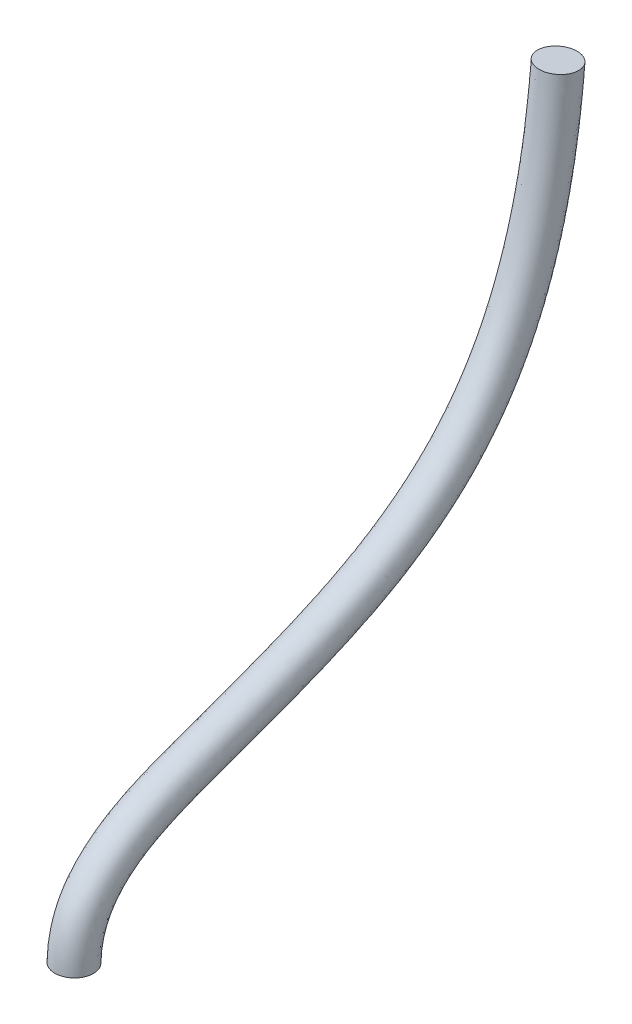
SolidWorks part; units mm, degrees
ref_plane "Front Plane" through (0, 0, 0) normal (0, 0, 1) x (1, 0, 0)
ref_plane "Top Plane" through (0, 0, 0) normal (0, 1, 0) x (1, 0, 0)
ref_plane "Right Plane" through (0, 0, 0) normal (1, 0, 0) x (0, 0, -1)
sketch "Sketch52" plane through (0, 0, 0) normal (1, 0, 0) x (0, 0, -1)
  spline S0 degree 3 poles (-42.3868, -8.3439) (-42.2577, -2.0864) (-18.8722, 6.4923) (-2.7323, 11.8872) (-0.4768, 38.3572) knots 0 0 0 0 0.247349 1 1 1 1
  point P2 (-10.097, 6.6746)
  point P4 (-23.6819, 5.7189)
  point P6 (-39.4514, 0.6672)
  point P8 (-14.3295, 7.016)
  point P9 (-23.955, 5.7189)
  point P10 (-44.2983, -10.938)
  point P11 (-38.1543, 0.7355)
  point P12 (-42.3868, -8.3439)
  point P13 (-41.0119, -3.1433)
  point P14 (-22.9102, 4.2704)
  point P15 (-13.2104, 3.9736)
  point P16 (-33.7376, 1.0625)
  point P17 (-6.457, 9.287)
  point P18 (-41.2296, -3.5548)
  point P19 (-33.4009, 0.7837)
  point P20 (-40.8891, -3.6958)
  point P21 (-21.6113, 5.5903)
  point P22 (-31.1322, 1.9627)
  dimension "D1" = 41.91
  dimension "D2" = 46.7011
sweep "Sweep2" add path "Sketch52" circular profile diameter 3.302 parameters "D3"=3.302
